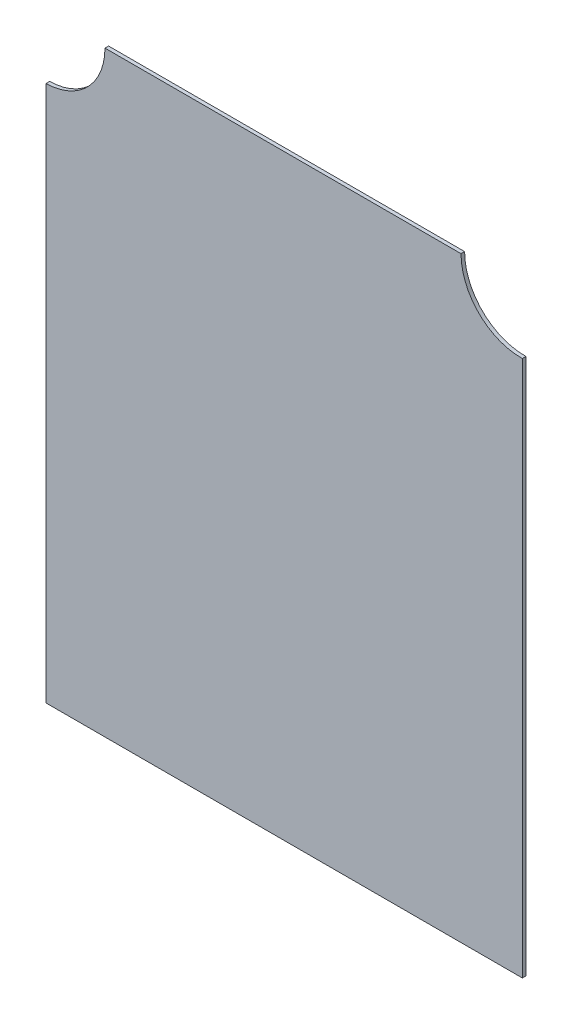
SolidWorks part; units mm, degrees
material "ДСП"
ref_plane "Спереди" through (0, 0, 0) normal (0, 0, 1) x (1, 0, 0)
ref_plane "Сверху" through (0, 0, 0) normal (0, 1, 0) x (1, 0, 0)
ref_plane "Справа" through (0, 0, 0) normal (1, 0, 0) x (0, 0, -1)
sketch "Эскиз1" plane through (0, 0, 0) normal (0, 0, 1) x (1, 0, 0)
  line L1 (0, 0) -> (396, 0)
  line L2 (0, 0) -> (0, 496)
  line L3 (0, 496) -> (396, 496)
  line L4 (396, 0) -> (396, 496)
  dimension "D1" = 496
  dimension "D2" = 396
extrude "Придание толщины" add sketch "Эскиз1" along normal blind 3
sketch "Эскиз3" plane through (0, 0, 3) normal (0, 0, 1) x (1, 0, 0)
  line L0 (0, 496) -> (0, 0) construction
  line L1 (0, 0) -> (396, 0) construction
  circle A0 centre (-1, 496) radius 50
  dimension "D1" = 100
  dimension "D2" = 1
  dimension "D3" = 496
extrude "Отверстие 1" cut sketch "Эскиз3" against normal blind 3
sketch "Эскиз4" plane through (0, 0, 3) normal (0, 0, 1) x (1, 0, 0)
  line L0 (0, 446.01) -> (0, 0) construction
  line L1 (0, 0) -> (396, 0) construction
  circle A0 centre (395, 496) radius 50
  dimension "D3" = 100
  dimension "D1" = 395
  dimension "D2" = 496
extrude "Отверстие 2" cut sketch "Эскиз4" against normal blind 3
sketch "Эскиз5" plane through (0, 0, 3) normal (0, 0, 1) x (1, 0, 0)
  line L0 (0, 446.01) -> (0, 0) construction
  line L1 (0, 0) -> (396, 0) construction
  circle A0 centre (0, 0) radius 4
  dimension "D1" = 8
extrude "Отверстие 3" [suppressed] cut sketch "Эскиз5" against normal blind 16
sketch "Эскиз6" plane through (0, 0, 3) normal (0, 0, 1) x (1, 0, 0)
  line L0 (0, 446.01) -> (0, 0) construction
  line L1 (0, 0) -> (396, 0) construction
  circle A0 centre (0, 0) radius 4
  dimension "D1" = 8
extrude "Отверстие 4" [suppressed] cut sketch "Эскиз6" against normal blind 16
sketch "Эскиз7" plane through (0, 0, 3) normal (0, 0, 1) x (1, 0, 0)
  line L0 (0, 446.01) -> (0, 0) construction
  line L1 (0, 0) -> (396, 0) construction
  circle A0 centre (0, 0) radius 4
  dimension "D1" = 8
extrude "Отверстие 5" [suppressed] cut sketch "Эскиз7" against normal blind 16
sketch "Эскиз8" plane through (0, 0, 3) normal (0, 0, 1) x (1, 0, 0)
  line L0 (0, 446.01) -> (0, 0) construction
  line L1 (0, 0) -> (396, 0) construction
  circle A0 centre (0, 0) radius 4
  dimension "D1" = 8
extrude "Отверстие 6" [suppressed] cut sketch "Эскиз8" against normal blind 16
sketch "Эскиз9" plane through (0, 0, 3) normal (0, 0, 1) x (1, 0, 0)
  line L0 (0, 446.01) -> (0, 0) construction
  line L1 (0, 0) -> (396, 0) construction
  circle A0 centre (0, 0) radius 4
  dimension "D1" = 8
extrude "Отверстие 7" [suppressed] cut sketch "Эскиз9" against normal blind 16
sketch "Эскиз10" plane through (0, 0, 3) normal (0, 0, 1) x (1, 0, 0)
  line L0 (0, 446.01) -> (0, 0) construction
  line L1 (0, 0) -> (396, 0) construction
  circle A0 centre (0, 0) radius 4
  dimension "D1" = 8
extrude "Отверстие 8" [suppressed] cut sketch "Эскиз10" against normal blind 16
sketch "Эскиз27" plane through (0, 0, 3) normal (0, 0, 1) x (1, 0, 0)
  line L2 (0, 446.01) -> (0, 0) construction
  line L3 (0, 0) -> (396, 0) construction
  circle A0 centre (0, 0) radius 4
  dimension "D1" = 8
  dimension "D3" = 0
extrude "Отверстие 9" [suppressed] cut sketch "Эскиз27" against normal blind 10
sketch "Эскиз29" plane through (0, 0, 3) normal (0, 0, 1) x (1, 0, 0)
  line L2 (0, 446.01) -> (0, 0) construction
  line L3 (0, 0) -> (396, 0) construction
  circle A0 centre (0, 0) radius 4
  dimension "D1" = 8
extrude "Отверстие 10" [suppressed] cut sketch "Эскиз29" against normal blind 10
sketch "Эскиз30" plane through (0, 0, 3) normal (0, 0, 1) x (1, 0, 0)
  line L1 (0, 0) -> (396, 0) construction
  line L3 (0, 446.01) -> (0, 0) construction
  circle A0 centre (0, 0) radius 4
  dimension "D1" = 8
extrude "Отверстие 11" [suppressed] cut sketch "Эскиз30" against normal blind 10
sketch "Эскиз31" plane through (0, 0, 3) normal (0, 0, 1) x (1, 0, 0)
  line L2 (0, 0) -> (396, 0) construction
  line L3 (0, 446.01) -> (0, 0) construction
  circle A0 centre (0, 0) radius 4
  dimension "D1" = 8
extrude "Отверстие 12" [suppressed] cut sketch "Эскиз31" against normal blind 10
sketch "Эскиз11" plane through (0, 496, 0) normal (0, 1, 0) x (1, 0, 0)
  line L0 (0, -3) -> (0, 0) construction
  line L1 (345, -3) -> (49, -3) construction
  circle A0 centre (0, -3) radius 2.5
  dimension "D3" = 0
  dimension "D1" = 5
extrude "Отверстие А1" [suppressed] cut sketch "Эскиз11" against normal blind 37
sketch "Эскиз12" plane through (0, 496, 0) normal (0, 1, 0) x (1, 0, 0)
  line L1 (0, -3) -> (0, 0) construction
  line L2 (345, -3) -> (49, -3) construction
  circle A0 centre (0, 5) radius 2.5
  dimension "D1" = 5
  dimension "D3" = 8
extrude "Отверстие А2" [suppressed] cut sketch "Эскиз12" against normal blind 37
sketch "Эскиз13" plane through (0, 496, 0) normal (0, 1, 0) x (1, 0, 0)
  line L1 (0, -3) -> (0, 0) construction
  line L2 (345, -3) -> (49, -3) construction
  circle A0 centre (0, -3) radius 4
  dimension "D1" = 8
  dimension "D3" = 0
extrude "Отверстие А3" [suppressed] cut sketch "Эскиз13" against normal blind 20
sketch "Эскиз14" plane through (0, 496, 0) normal (0, 1, 0) x (1, 0, 0)
  line L0 (0, -3) -> (0, 0) construction
  line L1 (345, -3) -> (49, -3) construction
  circle A0 centre (0, 5) radius 4
  dimension "D1" = 8
  dimension "D3" = 8
extrude "Отверстие А4" [suppressed] cut sketch "Эскиз14" against normal blind 20
sketch "Эскиз15" plane through (396, 0, 0) normal (1, 0, 0) x (0, 0, -1)
  line L0 (-3, 496) -> (0, 496) construction
  line L1 (-3, 0) -> (-3, 446.01) construction
  circle A0 centre (-3, 496) radius 2.5
  dimension "D2" = 0
  dimension "D3" = 0
  dimension "D1" = 5
extrude "Отверстие В1" [suppressed] cut sketch "Эскиз15" against normal blind 37
sketch "Эскиз16" plane through (396, 0, 0) normal (1, 0, 0) x (0, 0, -1)
  line L0 (-3, 496) -> (0, 496) construction
  line L1 (-3, 0) -> (-3, 446.01) construction
  circle A0 centre (-3, 496) radius 2.5
  dimension "D1" = 5
extrude "Отверстие В2" [suppressed] cut sketch "Эскиз16" against normal blind 37
sketch "Эскиз17" plane through (396, 0, 0) normal (1, 0, 0) x (0, 0, -1)
  line L1 (-3, 496) -> (0, 496) construction
  line L2 (-3, 0) -> (-3, 446.01) construction
  circle A0 centre (-3, 496) radius 4
  dimension "D1" = 8
  dimension "D2" = 0
  dimension "D3" = 0
extrude "Отверстие В3" [suppressed] cut sketch "Эскиз17" against normal blind 20
sketch "Эскиз18" plane through (396, 0, 0) normal (1, 0, 0) x (0, 0, -1)
  line L0 (-3, 496) -> (0, 496) construction
  line L1 (-3, 0) -> (-3, 446.01) construction
  circle A0 centre (-3, 496) radius 4
  dimension "D3" = 0
  dimension "D2" = 8
  dimension "D1" = 0
extrude "Отверстие В4" [suppressed] cut sketch "Эскиз18" against normal blind 20
sketch "Эскиз19" plane through (0, 0, 0) normal (0, -1, 0) x (1, 0, 0)
  line L0 (396, 3) -> (396, 0) construction
  line L1 (0, 3) -> (396, 3) construction
  circle A0 centre (396, 3) radius 2.5
  dimension "D2" = 0
  dimension "D3" = 0
  dimension "D1" = 5
extrude "Отверстие С1" [suppressed] cut sketch "Эскиз19" against normal blind 37
sketch "Эскиз20" plane through (0, 0, 0) normal (0, -1, 0) x (1, 0, 0)
  line L0 (396, 3) -> (396, 0) construction
  line L1 (0, 3) -> (396, 3) construction
  circle A0 centre (396, 3) radius 2.5
  dimension "D3" = 0
  dimension "D1" = 0
  dimension "D2" = 5
extrude "Отверстие С2" [suppressed] cut sketch "Эскиз20" against normal blind 37
sketch "Эскиз21" plane through (0, 0, 0) normal (0, -1, 0) x (1, 0, 0)
  line L0 (396, 3) -> (396, 0) construction
  line L1 (0, 3) -> (396, 3) construction
  circle A0 centre (396, 3) radius 4
  dimension "D1" = 8
  dimension "D2" = 0
  dimension "D3" = 0
extrude "Отверстие С3" [suppressed] cut sketch "Эскиз21" against normal blind 20
sketch "Эскиз22" plane through (0, 0, 0) normal (0, -1, 0) x (1, 0, 0)
  line L0 (396, 3) -> (396, 0) construction
  line L1 (0, 3) -> (396, 3) construction
  circle A0 centre (396, 3) radius 4
  dimension "D1" = 8
  dimension "D2" = 0
  dimension "D3" = 0
extrude "Отверстие С4" [suppressed] cut sketch "Эскиз22" against normal blind 20
sketch "Эскиз23" plane through (0, 0, 0) normal (-1, 0, 0) x (0, 0, 1)
  line L0 (3, 0) -> (0, 0) construction
  line L1 (3, 446.01) -> (3, 0) construction
  circle A0 centre (3, 0) radius 2.5
  dimension "D2" = 0
  dimension "D3" = 0
  dimension "D1" = 5
extrude "Отверстие Д1" [suppressed] cut sketch "Эскиз23" against normal blind 37
sketch "Эскиз24" plane through (0, 0, 0) normal (-1, 0, 0) x (0, 0, 1)
  line L0 (3, 0) -> (0, 0) construction
  line L1 (3, 446.01) -> (3, 0) construction
  circle A0 centre (3, 0) radius 2.5
  dimension "D2" = 0
  dimension "D3" = 0
  dimension "D1" = 5
extrude "Отверстие Д2" [suppressed] cut sketch "Эскиз24" against normal blind 37
sketch "Эскиз25" plane through (0, 0, 0) normal (-1, 0, 0) x (0, 0, 1)
  line L0 (3, 0) -> (0, 0) construction
  line L1 (3, 446.01) -> (3, 0) construction
  circle A0 centre (3, 0) radius 4
  dimension "D1" = 8
  dimension "D2" = 0
  dimension "D3" = 0
extrude "Отверстие Д3" [suppressed] cut sketch "Эскиз25" against normal blind 20
sketch "Эскиз26" plane through (0, 0, 0) normal (-1, 0, 0) x (0, 0, 1)
  line L0 (3, 0) -> (0, 0) construction
  line L1 (3, 446.01) -> (3, 0) construction
  circle A0 centre (3, 0) radius 4
  dimension "D1" = 8
  dimension "D2" = 0
  dimension "D3" = 0
extrude "Отверстие Д4" [suppressed] cut sketch "Эскиз26" against normal blind 20
equation "\"D1@Придание толщины\" = \"Thick\""
equation "\"D2@Эскиз1\"=\"Width\""
equation "\"D1@Эскиз1\"=\"Height\""
equation "\"D1\" = 100"
equation "\"X1\" = 1"
equation "\"Y1\" = 496"
equation "\"H1\" = 3"
equation "\"D1@Эскиз3\"=\"D1\""
equation "\"D2@Эскиз3\"=\"X1\""
equation "\"D3@Эскиз3\"=\"Y1\""
equation "\"D1@Отверстие 1\"=\"H1\""
equation "\"D2\" = 100"
equation "\"X2\" = 395"
equation "\"Y2\" = 496"
equation "\"H2\" = 3"
equation "\"D3\" = 0"
equation "\"X3\" = 0"
equation "\"Y3\" = 0"
equation "\"H3\" = 0"
equation "\"D4\" = 0"
equation "\"X4\" = 0"
equation "\"Y4\" = 0"
equation "\"H4\" = 0"
equation "\"D5\" = 0"
equation "\"X5\" = 0"
equation "\"Y5\" = 0"
equation "\"H5\" = 0"
equation "\"D6\" = 0"
equation "\"X6\" = 0"
equation "\"Y6\" = 0"
equation "\"H6\" = 0"
equation "\"D7\" = 0"
equation "\"X7\" = 0"
equation "\"Y7\" = 0"
equation "\"H7\" = 0"
equation "\"D8\" = 0"
equation "\"X8\" = 0"
equation "\"Y8\" = 0"
equation "\"H8\" = 0"
equation "\"D3@Эскиз4\"=\"D2\""
equation "\"D1@Эскиз4\"=\"X2\""
equation "\"D2@Эскиз4\"=\"Y2\""
equation "\"D1@Отверстие 2\"=\"H2\""
equation "\"D2@Эскиз5\"=\"X3\""
equation "\"D1@Эскиз5\"=\"D3\""
equation "\"D3@Эскиз5\"=\"Y3\""
equation "\"D1@Отверстие 3\" = \"H3\""
equation "\"D1@Эскиз6\"=\"D4\""
equation "\"D2@Эскиз6\"=\"X4\""
equation "\"D3@Эскиз6\"=\"Y4\""
equation "\"D1@Отверстие 4\" = \"H4\""
equation "\"D1@Эскиз7\"=\"D5\""
equation "\"D2@Эскиз7\"=\"X5\""
equation "\"D3@Эскиз7\"=\"Y5\""
equation "\"D1@Отверстие 5\" = \"H5\""
equation "\"D1@Эскиз8\"=\"D6\""
equation "\"D2@Эскиз8\"=\"X6\""
equation "\"D3@Эскиз8\"=\"Y6\""
equation "\"D1@Отверстие 6\" = \"H6\""
equation "\"D1@Эскиз9\"=\"D7\""
equation "\"D2@Эскиз9\"=\"X7\""
equation "\"D3@Эскиз9\"=\"Y7\""
equation "\"D1@Отверстие 7\" = \"H7\""
equation "\"D1@Эскиз10\"=\"D8\""
equation "\"D2@Эскиз10\"=\"X8\""
equation "\"D3@Эскиз10\"=\"Y8\""
equation "\"D1@Отверстие 8\" = \"H8\""
equation "\"Отверстие 1\"= IIF ( \"D1\" = 0 , \"suppressed\" , \"unsuppressed\" )"
equation "\"Отверстие 2\"= IIF ( \"D2\" = 0 , \"suppressed\" , \"unsuppressed\" )"
equation "\"Отверстие 3\"= IIF ( \"D3\" = 0 , \"suppressed\" , \"unsuppressed\" )"
equation "\"Отверстие 4\"= IIF ( \"D4\" = 0 , \"suppressed\" , \"unsuppressed\" )"
equation "\"Отверстие 5\"= IIF ( \"D5\" = 0 , \"suppressed\" , \"unsuppressed\" )"
equation "\"Отверстие 6\" = IIF ( \"D6\" = 0 , \"suppressed\" , \"unsuppressed\" )"
equation "\"Отверстие 7\"= IIF ( \"D7\" = 0 , \"suppressed\" , \"unsuppressed\" )"
equation "\"Отверстие 8\"= IIF ( \"D8\" = 0 , \"suppressed\" , \"unsuppressed\" )"
equation "\"DA1\"= 0"
equation "\"XA1\"= 0"
equation "\"YA1\"= 0"
equation "\"HA1\"= 0"
equation "\"DA2\"= 0"
equation "\"XA2\"= 0"
equation "\"YA2\"= 0"
equation "\"HA2\"= 0"
equation "\"DA3\"= 0"
equation "\"XA3\"= 0"
equation "\"YA3\"= 0"
equation "\"DA4\"= 0"
equation "\"XA4\"= 0"
equation "\"YA4\"= 0"
equation "\"HA4\"= 0"
equation "\"D1@Эскиз11\"=\"DA1\""
equation "\"D2@Эскиз11\"=\"XA1\""
equation "\"D3@Эскиз11\"=\"YA1\""
equation "\"D1@Отверстие А1\" = \"HA1\""
equation "\"D1@Эскиз12\"=\"DA2\""
equation "\"D2@Эскиз12\"=\"XA2\""
equation "\"HA3\"= 0"
equation "\"D1@Эскиз13\"=\"DA3\""
equation "\"D2@Эскиз13\"=\"XA3\""
equation "\"D3@Эскиз13\"=\"YA3\""
equation "\"D1@Отверстие А3\" = \"HA3\""
equation "\"D1@Отверстие А2\" = \"HA2\""
equation "\"D1@Эскиз14\"=\"DA4\""
equation "\"D2@Эскиз14\"=\"XA4\""
equation "\"Отверстие А1\"= IIF ( \"DA1\" = 0 , \"suppressed\" , \"unsuppressed\" )"
equation "\"Отверстие А2\"= IIF ( \"DA2\" = 0 , \"suppressed\" , \"unsuppressed\" )"
equation "\"Отверстие А3\"= IIF ( \"DA3\" = 0 , \"suppressed\" , \"unsuppressed\" )"
equation "\"Отверстие А4\"= IIF ( \"DA4\" = 0 , \"suppressed\" , \"unsuppressed\" )"
equation "\"DB1\"= 0"
equation "\"XB1\"= 0"
equation "\"YB1\"= 0"
equation "\"HB1\"= 0"
equation "\"DB2\"= 0"
equation "\"XB2\"= 0"
equation "\"YB2\"= 0"
equation "\"HB2\"= 0"
equation "\"DB3\"= 0"
equation "\"XB3\"= 0"
equation "\"YB3\"= 0"
equation "\"HB3\"= 0"
equation "\"DB4\"= 0"
equation "\"XB4\"= 0"
equation "\"YB4\"= 0"
equation "\"HB4\"= 0"
equation "\"DC1\"= 0"
equation "\"XC1\"= 0"
equation "\"YC1\"= 0"
equation "\"HC1\"= 0"
equation "\"DC2\"= 0"
equation "\"XC2\"= 0"
equation "\"YC2\"= 0"
equation "\"HC2\"= 0"
equation "\"DC3\"= 0"
equation "\"XC3\"= 0"
equation "\"YC3\"= 0"
equation "\"HC3\"= 0"
equation "\"DC4\"= 0"
equation "\"XC4\"= 0"
equation "\"YC4\"= 0"
equation "\"HC4\"= 0"
equation "\"DD1\"= 0"
equation "\"XD1\"= 0"
equation "\"YD1\"= 0"
equation "\"HD1\"= 0"
equation "\"DD2\"= 0"
equation "\"XD2\"= 0"
equation "\"YD2\"= 0"
equation "\"HD2\"= 0"
equation "\"DD3\"= 0"
equation "\"XD3\"= 0"
equation "\"YD3\"= 0"
equation "\"HD3\"= 0"
equation "\"DD4\"= 0"
equation "\"XD4\"= 0"
equation "\"YD4\"= 0"
equation "\"HD4\"= 0"
equation "\"D1@Эскиз15\"=\"DB1\""
equation "\"D2@Эскиз15\"=\"XB1\""
equation "\"D3@Эскиз15\"=\"YB1\""
equation "\"D1@Отверстие В1\" = \"HB1\""
equation "\"D1@Эскиз16\"=\"DB2\""
equation "\"D2@Эскиз16\"=\"XB2\""
equation "\"D3@Эскиз16\"=\"YB2\""
equation "\"D1@Отверстие В2\" = \"HB2\""
equation "\"D1@Эскиз17\"=\"DB3\""
equation "\"D2@Эскиз17\"=\"XB3\""
equation "\"D3@Эскиз17\"=\"YB3\""
equation "\"D1@Отверстие В3\" = \"HB3\""
equation "\"D1@Эскиз18\"=\"XB4\""
equation "\"D2@Эскиз18\"=\"DB4\""
equation "\"D3@Эскиз18\"=\"YB4\""
equation "\"D1@Отверстие В4\" = \"HB4\""
equation "\"D1@Эскиз19\"=\"DC1\""
equation "\"D2@Эскиз19\"=\"XC1\""
equation "\"D3@Эскиз19\"=\"YC1\""
equation "\"D1@Отверстие С1\" = \"HC1\""
equation "\"D1@Эскиз20\"=\"XC2\""
equation "\"D2@Эскиз20\"=\"DC2\""
equation "\"D3@Эскиз20\"=\"YC2\""
equation "\"D1@Отверстие С2\" = \"HC2\""
equation "\"D1@Эскиз21\"=\"DC3\""
equation "\"D2@Эскиз21\"=\"XC3\""
equation "\"D3@Эскиз21\"=\"YC3\""
equation "\"D1@Отверстие С3\" = \"HC3\""
equation "\"D1@Эскиз22\"=\"DC4\""
equation "\"D2@Эскиз22\"=\"XC4\""
equation "\"D3@Эскиз22\"=\"YC4\""
equation "\"D1@Отверстие С4\" = \"HC4\""
equation "\"D1@Эскиз23\"=\"DD1\""
equation "\"D2@Эскиз23\"=\"XD1\""
equation "\"D3@Эскиз23\"=\"YD1\""
equation "\"D1@Отверстие Д1\" = \"HD1\""
equation "\"D1@Эскиз24\"=\"DD2\""
equation "\"D2@Эскиз24\"=\"XD2\""
equation "\"D3@Эскиз24\"=\"YD2\""
equation "\"D1@Отверстие Д2\" = \"HD2\""
equation "\"D1@Эскиз25\"=\"DD3\""
equation "\"D2@Эскиз25\"=\"XD3\""
equation "\"D3@Эскиз25\"=\"YD3\""
equation "\"D1@Отверстие Д3\" = \"HD3\""
equation "\"D1@Эскиз26\"=\"DD4\""
equation "\"D2@Эскиз26\"=\"XD4\""
equation "\"D3@Эскиз26\"=\"YD4\""
equation "\"D1@Отверстие Д4\" = \"HD4\""
equation "\"Отверстие В1\"= IIF ( \"DB1\" = 0 , \"suppressed\" , \"unsuppressed\" )"
equation "\"Отверстие В2\"= IIF ( \"DB2\" = 0 , \"suppressed\" , \"unsuppressed\" )"
equation "\"Отверстие В3\"= IIF ( \"DB3\" = 0 , \"suppressed\" , \"unsuppressed\" )"
equation "\"Отверстие В4\"= IIF ( \"DB4\" = 0 , \"suppressed\" , \"unsuppressed\" )"
equation "\"Отверстие С1\"= IIF ( \"DC1\" = 0 , \"suppressed\" , \"unsuppressed\" )"
equation "\"Отверстие С2\"= IIF ( \"DC2\" = 0 , \"suppressed\" , \"unsuppressed\" )"
equation "\"Отверстие С3\"= IIF ( \"DC3\" = 0 , \"suppressed\" , \"unsuppressed\" )"
equation "\"Отверстие С4\"= IIF ( \"DC4\" = 0 , \"suppressed\" , \"unsuppressed\" )"
equation "\"Отверстие Д1\"= IIF ( \"DD1\" = 0 , \"suppressed\" , \"unsuppressed\" )"
equation "\"Отверстие Д2\"= IIF ( \"DD2\" = 0 , \"suppressed\" , \"unsuppressed\" )"
equation "\"Отверстие Д3\"= IIF ( \"DD3\" = 0 , \"suppressed\" , \"unsuppressed\" )"
equation "\"Отверстие Д4\"= IIF ( \"DD4\" = 0 , \"suppressed\" , \"unsuppressed\" )"
equation "\"D9\" = 0"
equation "\"X9\" = 0"
equation "\"Y9\" = 0"
equation "\"H9\" = 0"
equation "\"D10\" = 0"
equation "\"X10\" = 0"
equation "\"Y10\" = 0"
equation "\"H10\" = 0"
equation "\"D11\" = 0"
equation "\"X11\" = 0"
equation "\"Y11\" = 0"
equation "\"H11\" = 0"
equation "\"D12\" = 0"
equation "\"X12\" = 0"
equation "\"Y12\" = 0"
equation "\"H12\" = 0"
equation "\"D1@Эскиз27\"=\"D9\""
equation "\"D2@Эскиз27\"=\"X9\""
equation "\"D3@Эскиз27\"=\"Y9\""
equation "\"D1@Отверстие 9\" = \"H9\""
equation "\"D1@Эскиз29\"=\"D10\""
equation "\"D2@Эскиз29\"=\"X10\""
equation "\"D3@Эскиз29\"=\"Y10\""
equation "\"D1@Отверстие 10\" = \"H10\""
equation "\"D1@Эскиз30\"=\"D11\""
equation "\"D2@Эскиз30\"=\"X11\""
equation "\"D3@Эскиз30\"=\"Y11\""
equation "\"D1@Отверстие 11\" = \"H11\""
equation "\"D1@Эскиз31\"=\"D12\""
equation "\"D2@Эскиз31\"=\"X12\""
equation "\"D3@Эскиз31\"=\"Y12\""
equation "\"D1@Отверстие 12\" = \"H12\""
equation "\"Отверстие 9\"= IIF ( \"D9\" = 0 , \"suppressed\" , \"unsuppressed\" )"
equation "\"Отверстие 10\"= IIF ( \"D10\" = 0 , \"suppressed\" , \"unsuppressed\" )"
equation "\"Отверстие 11\"= IIF ( \"D11\" = 0 , \"suppressed\" , \"unsuppressed\" )"
equation "\"Отверстие 12\"= IIF ( \"D12\" = 0 , \"suppressed\" , \"unsuppressed\" )"
equation "\"Height\" = 496"
equation "\"Width\" = 396"
equation "\"Thick\" = 3"
